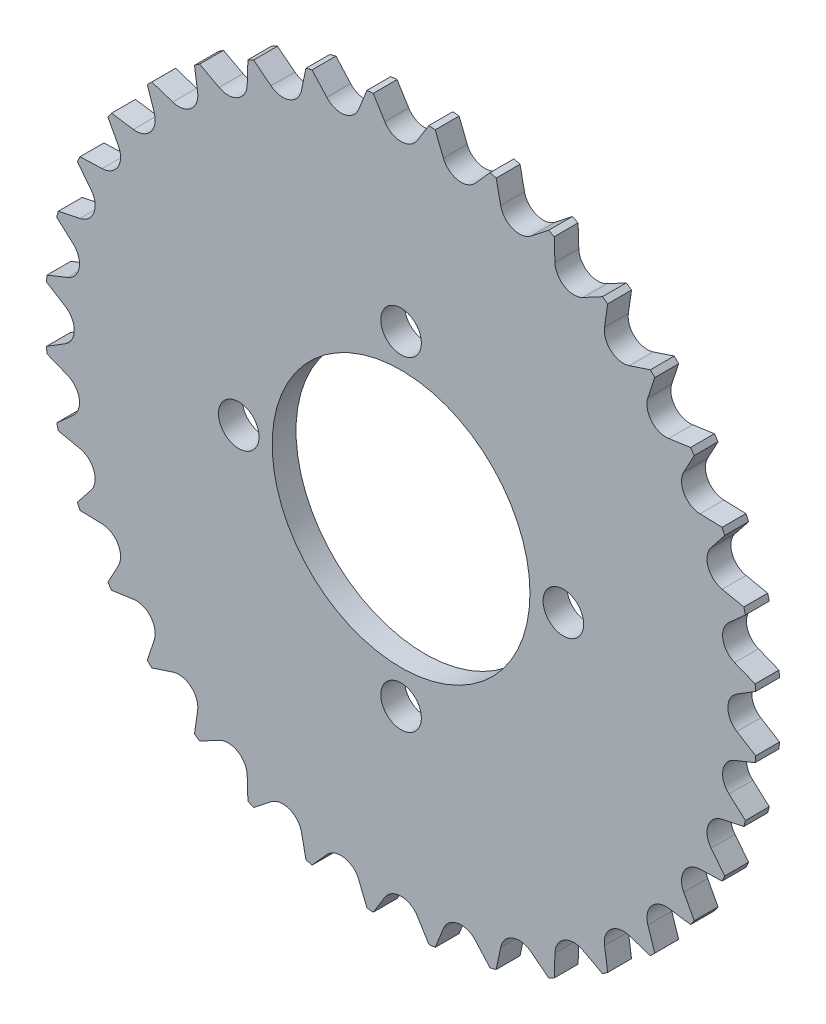
SolidWorks part; units mm, degrees
material "Plain Carbon Steel"
ref_plane "Front Plane" through (0, 0, 0) normal (0, 0, 1) x (1, 0, 0)
ref_plane "Top Plane" through (0, 0, 0) normal (0, 1, 0) x (1, 0, 0)
ref_plane "Right Plane" through (0, 0, 0) normal (1, 0, 0) x (0, 0, -1)
sketch "Sketch1" plane through (0, 0, 0) normal (0, 0, 1) x (1, 0, 0)
  line L0 (3.4006, 70.3439) -> (6.0855, 74.679)
  line L1 (3.4006, 70.3439) -> (8.8661, 69.8657) construction
  line L2 (6.9749, 74.6012) -> (8.8661, 69.8657)
  line L3 (3.4006, 70.3439) -> (0, 0) construction
  line L4 (0, 0) -> (8.8661, 69.8657) construction
  line L5 (15.5641, 68.6847) -> (18.9609, 72.4877)
  line L6 (19.8233, 72.2567) -> (20.8635, 67.2647)
  line L7 (27.2546, 64.9386) -> (31.2602, 68.094)
  line L8 (32.0693, 67.7166) -> (32.2269, 62.6199)
  line L9 (38.117, 59.2193) -> (42.6097, 61.6312)
  line L10 (43.341, 61.1191) -> (42.6111, 56.0725)
  line L11 (47.8212, 51.7007) -> (52.6645, 53.2958)
  line L12 (53.2958, 52.6645) -> (51.7007, 47.8212)
  line L13 (56.0725, 42.6111) -> (61.1191, 43.341)
  line L14 (61.6312, 42.6097) -> (59.2193, 38.117)
  line L15 (62.6199, 32.2269) -> (67.7166, 32.0693)
  line L16 (68.094, 31.2602) -> (64.9386, 27.2546)
  line L17 (67.2647, 20.8635) -> (72.2567, 19.8233)
  line L18 (72.4877, 18.9609) -> (68.6847, 15.5641)
  line L19 (69.8657, 8.8661) -> (74.6012, 6.9749)
  line L20 (74.679, 6.0855) -> (70.3439, 3.4006)
  line L21 (70.3439, -3.4006) -> (74.679, -6.0855)
  line L22 (74.6012, -6.9749) -> (69.8657, -8.8661)
  line L23 (68.6847, -15.5641) -> (72.4877, -18.9609)
  line L24 (72.2567, -19.8233) -> (67.2647, -20.8635)
  line L25 (64.9386, -27.2546) -> (68.094, -31.2602)
  line L26 (67.7166, -32.0693) -> (62.6199, -32.2269)
  line L27 (59.2193, -38.117) -> (61.6312, -42.6097)
  line L28 (61.1191, -43.341) -> (56.0725, -42.6111)
  line L29 (51.7007, -47.8212) -> (53.2958, -52.6645)
  line L30 (52.6645, -53.2958) -> (47.8212, -51.7007)
  line L31 (42.6111, -56.0725) -> (43.341, -61.1191)
  line L32 (42.6097, -61.6312) -> (38.117, -59.2193)
  line L33 (32.2269, -62.6199) -> (32.0693, -67.7166)
  line L34 (31.2602, -68.094) -> (27.2546, -64.9386)
  line L35 (20.8635, -67.2647) -> (19.8233, -72.2567)
  line L36 (18.9609, -72.4877) -> (15.5641, -68.6847)
  line L37 (8.8661, -69.8657) -> (6.9749, -74.6012)
  line L38 (6.0855, -74.679) -> (3.4006, -70.3439)
  line L39 (-3.4006, -70.3439) -> (-6.0855, -74.679)
  line L40 (-6.9749, -74.6012) -> (-8.8661, -69.8657)
  line L41 (-15.5641, -68.6847) -> (-18.9609, -72.4877)
  line L42 (-19.8233, -72.2567) -> (-20.8635, -67.2647)
  line L43 (-27.2546, -64.9386) -> (-31.2602, -68.094)
  line L44 (-32.0693, -67.7166) -> (-32.2269, -62.6199)
  line L45 (-38.117, -59.2193) -> (-42.6097, -61.6312)
  line L46 (-43.341, -61.1191) -> (-42.6111, -56.0725)
  line L47 (-47.8212, -51.7007) -> (-52.6645, -53.2958)
  line L48 (-53.2958, -52.6645) -> (-51.7007, -47.8212)
  line L49 (-56.0725, -42.6111) -> (-61.1191, -43.341)
  line L50 (-61.6312, -42.6097) -> (-59.2193, -38.117)
  line L51 (-62.6199, -32.2269) -> (-67.7166, -32.0693)
  line L52 (-68.094, -31.2602) -> (-64.9386, -27.2546)
  line L53 (-67.2647, -20.8635) -> (-72.2567, -19.8233)
  line L54 (-72.4877, -18.9609) -> (-68.6847, -15.5641)
  line L55 (-69.8657, -8.8661) -> (-74.6012, -6.9749)
  line L56 (-74.679, -6.0855) -> (-70.3439, -3.4006)
  line L57 (-70.3439, 3.4006) -> (-74.679, 6.0855)
  line L58 (-74.6012, 6.9749) -> (-69.8657, 8.8661)
  line L59 (-68.6847, 15.5641) -> (-72.4877, 18.9609)
  line L60 (-72.2567, 19.8233) -> (-67.2647, 20.8635)
  line L61 (-64.9386, 27.2546) -> (-68.094, 31.2602)
  line L62 (-67.7166, 32.0693) -> (-62.6199, 32.2269)
  line L63 (-59.2193, 38.117) -> (-61.6312, 42.6097)
  line L64 (-61.1191, 43.341) -> (-56.0725, 42.6111)
  line L65 (-51.7007, 47.8212) -> (-53.2958, 52.6645)
  line L66 (-52.6645, 53.2958) -> (-47.8212, 51.7007)
  line L67 (-42.6111, 56.0725) -> (-43.341, 61.1191)
  line L68 (-42.6097, 61.6312) -> (-38.117, 59.2193)
  line L69 (-32.2269, 62.6199) -> (-32.0693, 67.7166)
  line L70 (-31.2602, 68.094) -> (-27.2546, 64.9386)
  line L71 (-20.8635, 67.2647) -> (-19.8233, 72.2567)
  line L72 (-18.9609, 72.4877) -> (-15.5641, 68.6847)
  line L73 (-8.8661, 69.8657) -> (-6.9749, 74.6012)
  line L74 (-6.0855, 74.679) -> (-3.4006, 70.3439)
  line L83 (0, 72.45) -> (0, 0) construction
  line L84 (0, 0) -> (6.5105, 74.4157) construction
  circle A0 centre (0, 0) radius 72.45 construction
  arc A1 (-3.9985, 72.3396) -> (3.4006, 70.3439) centre (0, 72.45) ccw
  arc A2 (4.6139, 72.3029) -> (8.0115, 72.0057) centre (0, 0) cw
  arc A3 (6.0855, 74.679) -> (6.9749, 74.6012) centre (6.5105, 74.4157) cw
  arc A4 (8.6239, 71.9349) -> (15.5641, 68.6847) centre (12.5808, 71.3493) ccw
  arc A5 (18.9609, 72.4877) -> (19.8233, 72.2567) centre (19.3338, 72.1547) cw
  arc A6 (20.9843, 69.3445) -> (27.2546, 64.9386) centre (24.7794, 68.0807) ccw
  arc A7 (31.2602, 68.094) -> (32.0693, 67.7166) centre (31.5696, 67.7012) cw
  arc A8 (32.707, 64.6472) -> (38.117, 59.2193) centre (36.225, 62.7435) ccw
  arc A9 (42.6097, 61.6312) -> (43.341, 61.1191) centre (42.8462, 61.1907) cw
  arc A10 (43.436, 57.9855) -> (47.8212, 51.7007) centre (46.57, 55.4999) ccw
  arc A11 (52.6645, 53.2958) -> (53.2958, 52.6645) centre (52.8209, 52.8209) cw
  arc A12 (52.8452, 49.562) -> (56.0725, 42.6111) centre (55.4999, 46.57) ccw
  arc A13 (61.1191, 43.341) -> (61.6312, 42.6097) centre (61.1907, 42.8462) cw
  arc A14 (60.6487, 39.6326) -> (62.6199, 32.2269) centre (62.7435, 36.225) ccw
  arc A15 (67.7166, 32.0693) -> (68.094, 31.2602) centre (67.7012, 31.5696) cw
  arc A16 (66.6094, 28.4989) -> (67.2647, 20.8635) centre (68.0807, 24.7794) ccw
  arc A17 (72.2567, 19.8233) -> (72.4877, 18.9609) centre (72.1547, 19.3338) cw
  arc A18 (70.5463, 16.4994) -> (69.8657, 8.8661) centre (71.3493, 12.5808) ccw
  arc A19 (74.6012, 6.9749) -> (74.679, 6.0855) centre (74.4157, 6.5105) cw
  arc A20 (72.3396, 3.9985) -> (70.3439, -3.4006) centre (72.45, 0) ccw
  arc A21 (74.679, -6.0855) -> (74.6012, -6.9749) centre (74.4157, -6.5105) cw
  arc A22 (71.9349, -8.6239) -> (68.6847, -15.5641) centre (71.3493, -12.5808) ccw
  arc A23 (72.4877, -18.9609) -> (72.2567, -19.8233) centre (72.1547, -19.3338) cw
  arc A24 (69.3445, -20.9843) -> (64.9386, -27.2546) centre (68.0807, -24.7794) ccw
  arc A25 (68.094, -31.2602) -> (67.7166, -32.0693) centre (67.7012, -31.5696) cw
  arc A26 (64.6472, -32.707) -> (59.2193, -38.117) centre (62.7435, -36.225) ccw
  arc A27 (61.6312, -42.6097) -> (61.1191, -43.341) centre (61.1907, -42.8462) cw
  arc A28 (57.9855, -43.436) -> (51.7007, -47.8212) centre (55.4999, -46.57) ccw
  arc A29 (53.2958, -52.6645) -> (52.6645, -53.2958) centre (52.8209, -52.8209) cw
  arc A30 (49.562, -52.8452) -> (42.6111, -56.0725) centre (46.57, -55.4999) ccw
  arc A31 (43.341, -61.1191) -> (42.6097, -61.6312) centre (42.8462, -61.1907) cw
  arc A32 (39.6326, -60.6487) -> (32.2269, -62.6199) centre (36.225, -62.7435) ccw
  arc A33 (32.0693, -67.7166) -> (31.2602, -68.094) centre (31.5696, -67.7012) cw
  arc A34 (28.4989, -66.6094) -> (20.8635, -67.2647) centre (24.7794, -68.0807) ccw
  arc A35 (19.8233, -72.2567) -> (18.9609, -72.4877) centre (19.3338, -72.1547) cw
  arc A36 (16.4994, -70.5463) -> (8.8661, -69.8657) centre (12.5808, -71.3493) ccw
  arc A37 (6.9749, -74.6012) -> (6.0855, -74.679) centre (6.5105, -74.4157) cw
  arc A38 (3.9985, -72.3396) -> (-3.4006, -70.3439) centre (0, -72.45) ccw
  arc A39 (-6.0855, -74.679) -> (-6.9749, -74.6012) centre (-6.5105, -74.4157) cw
  arc A40 (-8.6239, -71.9349) -> (-15.5641, -68.6847) centre (-12.5808, -71.3493) ccw
  arc A41 (-18.9609, -72.4877) -> (-19.8233, -72.2567) centre (-19.3338, -72.1547) cw
  arc A42 (-20.9843, -69.3445) -> (-27.2546, -64.9386) centre (-24.7794, -68.0807) ccw
  arc A43 (-31.2602, -68.094) -> (-32.0693, -67.7166) centre (-31.5696, -67.7012) cw
  arc A44 (-32.707, -64.6472) -> (-38.117, -59.2193) centre (-36.225, -62.7435) ccw
  arc A45 (-42.6097, -61.6312) -> (-43.341, -61.1191) centre (-42.8462, -61.1907) cw
  arc A46 (-43.436, -57.9855) -> (-47.8212, -51.7007) centre (-46.57, -55.4999) ccw
  arc A47 (-52.6645, -53.2958) -> (-53.2958, -52.6645) centre (-52.8209, -52.8209) cw
  arc A48 (-52.8452, -49.562) -> (-56.0725, -42.6111) centre (-55.4999, -46.57) ccw
  arc A49 (-61.1191, -43.341) -> (-61.6312, -42.6097) centre (-61.1907, -42.8462) cw
  arc A50 (-60.6487, -39.6326) -> (-62.6199, -32.2269) centre (-62.7435, -36.225) ccw
  arc A51 (-67.7166, -32.0693) -> (-68.094, -31.2602) centre (-67.7012, -31.5696) cw
  arc A52 (-66.6094, -28.4989) -> (-67.2647, -20.8635) centre (-68.0807, -24.7794) ccw
  arc A53 (-72.2567, -19.8233) -> (-72.4877, -18.9609) centre (-72.1547, -19.3338) cw
  arc A54 (-70.5463, -16.4994) -> (-69.8657, -8.8661) centre (-71.3493, -12.5808) ccw
  arc A55 (-74.6012, -6.9749) -> (-74.679, -6.0855) centre (-74.4157, -6.5105) cw
  arc A56 (-72.3396, -3.9985) -> (-70.3439, 3.4006) centre (-72.45, 0) ccw
  arc A57 (-74.679, 6.0855) -> (-74.6012, 6.9749) centre (-74.4157, 6.5105) cw
  arc A58 (-71.9349, 8.6239) -> (-68.6847, 15.5641) centre (-71.3493, 12.5808) ccw
  arc A59 (-72.4877, 18.9609) -> (-72.2567, 19.8233) centre (-72.1547, 19.3338) cw
  arc A60 (-69.3445, 20.9843) -> (-64.9386, 27.2546) centre (-68.0807, 24.7794) ccw
  arc A61 (-68.094, 31.2602) -> (-67.7166, 32.0693) centre (-67.7012, 31.5696) cw
  arc A62 (-64.6472, 32.707) -> (-59.2193, 38.117) centre (-62.7435, 36.225) ccw
  arc A63 (-61.6312, 42.6097) -> (-61.1191, 43.341) centre (-61.1907, 42.8462) cw
  arc A64 (-57.9855, 43.436) -> (-51.7007, 47.8212) centre (-55.4999, 46.57) ccw
  arc A65 (-53.2958, 52.6645) -> (-52.6645, 53.2958) centre (-52.8209, 52.8209) cw
  arc A66 (-49.562, 52.8452) -> (-42.6111, 56.0725) centre (-46.57, 55.4999) ccw
  arc A67 (-43.341, 61.1191) -> (-42.6097, 61.6312) centre (-42.8462, 61.1907) cw
  arc A68 (-39.6326, 60.6487) -> (-32.2269, 62.6199) centre (-36.225, 62.7435) ccw
  arc A69 (-32.0693, 67.7166) -> (-31.2602, 68.094) centre (-31.5696, 67.7012) cw
  arc A70 (-28.4989, 66.6094) -> (-20.8635, 67.2647) centre (-24.7794, 68.0807) ccw
  arc A71 (-19.8233, 72.2567) -> (-18.9609, 72.4877) centre (-19.3338, 72.1547) cw
  arc A72 (-16.4994, 70.5463) -> (-8.8661, 69.8657) centre (-12.5808, 71.3493) ccw
  arc A73 (-6.9749, 74.6012) -> (-6.0855, 74.679) centre (-6.5105, 74.4157) cw
  point P289 (0, 0)
  dimension "D1" = 144.9
  dimension "D2" = 4
  dimension "D5" = 0.5
  dimension "D6" = 74.7
  dimension "D3" = 5
  dimension "D4" = 36
extrude "Boss-Extrude1" add sketch "Sketch1" along normal blind 5 contours L74 A73 L73 A72 L72 A71 L71 A70 L70 A69 L69 A68 L68 A67 L67 A66 L66 A65 L65 A64 L64 A63 L63 A62 L62 A61 L61 A60 L60 A59 L59 A58 L58 A57 L57 A56 | A3 L0 A2 L2 region at (-0.0022, -0.0255, 0) region at (6.4054, 73.214, 0)
sketch "Sketch5" plane through (0, 0, 0) normal (0, 0, -1) x (-1, 0, 0)
  line L0 (0, 68.45) -> (2.9886, 68.1885)
  line L1 (0, 68.45) -> (0.611, 75.4338)
  line L2 (11.8862, 67.4101) -> (12.4972, 74.3939)
  line L3 (0.611, 75.4338) -> (12.4972, 74.3939)
  line L4 (8.8976, 67.6716) -> (11.8862, 67.4101)
  arc A0 (2.9886, 68.1885) -> (8.8976, 67.6716) centre (6.3977, 73.1259) ccw
  arc A3 (-3.4006, 70.3439) -> (3.4006, 70.3439) centre (0, 72.45) ccw construction
  arc A5 (-3.4006, 70.3439) -> (3.4006, 70.3439) centre (0, 72.45) ccw construction
  arc A7 (8.8661, 69.8657) -> (15.5641, 68.6847) centre (12.5808, 71.3493) ccw construction
  arc A8 (6.9749, 74.6012) -> (6.0855, 74.679) centre (6.5105, 74.4157) ccw construction
  point P19 (0, 68.45)
  point P22 (11.8862, 67.4101)
  dimension "D2" = 3
  dimension "D3" = 3
  dimension "D4" = 6
extrude "Cut-Extrude2" [suppressed] cut sketch "Sketch5" against normal blind 10
sketch "Sketch9" plane through (0, 0, 0) normal (0, 0, -1) x (-1, 0, 0)
  circle A0 centre (0, 0) radius 74.5
  circle A1 centre (0, 0) radius 100
  dimension "D1" = 149
  dimension "D2" = 200
extrude "Cut-Extrude5" cut sketch "Sketch9" against normal blind 10
sketch "Sketch10" plane through (0, 0, 5) normal (0, 0, 1) x (1, 0, 0)
  circle A0 centre (0, 0) radius 27
  circle A1 centre (0, 34) radius 4.25
  circle A2 centre (34, 0) radius 4.25
  circle A3 centre (0, -34) radius 4.25
  circle A4 centre (-34, 0) radius 4.25
  point P14 (0, 0)
  dimension "D1" = 54
  dimension "D2" = 8.5
  dimension "D3" = 34
  dimension "D4" = 4
extrude "Cut-Extrude6" cut sketch "Sketch10" against normal through all
sketch "Sketch11" plane through (0, 0, 5) normal (0, 0, 1) x (1, 0, 0)
  line L1 (88.2775, 0) -> (-102.8822, 0)
  line L2 (88.2775, 0) -> (88.2775, -76.2691)
  line L3 (88.2775, -76.2691) -> (-102.8822, -76.2691)
  line L4 (-102.8822, 0) -> (-102.8822, -76.2691)
  circle A0 centre (0, 0) radius 55
  dimension "D1" = 110
extrude "Cut-Extrude7" [suppressed] cut sketch "Sketch11" against normal blind 10 contours L1 A0 | A0 L1 L4 L3 L2 | L1 A0
equation "\"Teeth\"= 36"
equation "\"D4@Sketch1\"=\"Teeth\""
equation "\"D6@Sketch1\"=83/40*\"Teeth\""
equation "\"D1@Sketch1\"=161/40*\"Teeth\""
equation "\"D3@Sketch1\"=4.5/\"Teeth\"*40"
